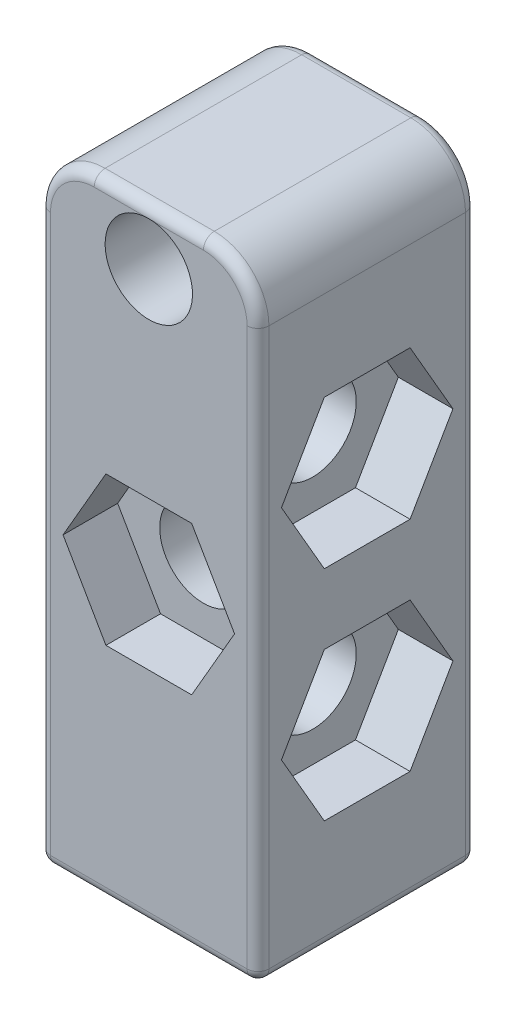
SolidWorks part; units mm, degrees
ref_plane "Alzado" through (0, 0, 0) normal (0, 0, 1) x (1, 0, 0)
ref_plane "Planta" through (0, 0, 0) normal (0, 1, 0) x (1, 0, 0)
ref_plane "Vista lateral" through (0, 0, 0) normal (1, 0, 0) x (0, 0, -1)
sketch "Croquis1" plane through (0, 0, 0) normal (0, 1, 0) x (1, 0, 0)
  line L1 (0, 0) -> (20, 0)
  line L2 (0, 0) -> (0, 20)
  line L3 (0, 20) -> (20, 20)
  line L4 (20, 0) -> (20, 20)
  dimension "D1" = 20
  dimension "D2" = 20
extrude "Saliente-Extruir1" add sketch "Croquis1" along normal blind 50 and the other way blind 7
sketch "Croquis2" plane through (0, 0, 0) normal (0, 0, 1) x (1, 0, 0)
  line L0 (0, 50) -> (0, -7) construction
  line L1 (0, 50) -> (20, 50) construction
  circle A0 centre (10, 45) radius 4
  circle A1 centre (10, 20) radius 4
  dimension "D1" = 8
  dimension "D2" = 8
  dimension "D3" = 10
  dimension "D4" = 5
  dimension "D5" = 25
extrude "Cortar-Extruir1" cut sketch "Croquis2" against normal through all
sketch "Croquis3" plane through (0, 0, 0) normal (0, 0, 1) x (1, 0, 0)
  line L1 (13.926, 26.8) -> (6.074, 26.8)
  line L2 (6.074, 26.8) -> (2.148, 20)
  line L3 (2.148, 20) -> (6.074, 13.2)
  line L4 (6.074, 13.2) -> (13.926, 13.2)
  line L5 (13.926, 13.2) -> (17.852, 20)
  line L6 (17.852, 20) -> (13.926, 26.8)
  circle A0 centre (10, 20) radius 7.852 construction
  dimension "D1" = 13.6
extrude "Cortar-Extruir2" cut sketch "Croquis3" against normal blind 5
sketch "Croquis4" plane through (0, 0, 0) normal (-1, 0, 0) x (0, 0, 1)
  line L0 (-20, 45) -> (0, 45) construction
  line L1 (-20, 50) -> (-20, -7) construction
  circle A0 centre (-10, 30) radius 4
  circle A1 centre (-10, 10) radius 4
  dimension "D1" = 8
  dimension "D2" = 8
  dimension "D5" = 10
  dimension "D3" = 15
  dimension "D4" = 20
extrude "Cortar-Extruir3" cut sketch "Croquis4" against normal through all
sketch "Croquis5" plane through (20, 0, 0) normal (-1, 0, 0) x (0, 0, 1)
  line L1 (-6.074, 23.2) -> (-2.148, 30)
  line L2 (-2.148, 30) -> (-6.074, 36.8)
  line L3 (-6.074, 36.8) -> (-13.926, 36.8)
  line L4 (-13.926, 36.8) -> (-17.852, 30)
  line L5 (-17.852, 30) -> (-13.926, 23.2)
  line L6 (-13.926, 23.2) -> (-6.074, 23.2)
  line L7 (-6.074, 16.8) -> (-13.926, 16.8)
  line L8 (-13.926, 16.8) -> (-17.852, 10)
  line L9 (-17.852, 10) -> (-13.926, 3.2)
  line L10 (-13.926, 3.2) -> (-6.074, 3.2)
  line L11 (-6.074, 3.2) -> (-2.148, 10)
  line L12 (-2.148, 10) -> (-6.074, 16.8)
  circle A0 centre (-10, 30) radius 6.8 construction
  circle A1 centre (-10, 10) radius 6.8 construction
  dimension "D1" = 13.6
  dimension "D2" = 13.6
extrude "Cortar-Extruir4" cut sketch "Croquis5" along normal blind 5
fillet "Redondeo1" radius 5 2 edges at (0, 50, -10) (20, 50, -10)
fillet "Redondeo2" radius 1 4 edges at (0, -7, -10) (10, -7, -20) (20, -7, -10) (10, -7, 0)
fillet "Redondeo3" radius 1 14 edges at (0.2929, -6.7071, -0.2929) (0, 19.5, 0) (1.4645, 48.5355, 0) (10, 50, 0) (18.5355, 48.5355, 0) (19.7071, -6.7071, -0.2929) (20, 19.5, 0) (0.2929, -6.7071, -19.7071) (0, 19.5, -20) (1.4645, 48.5355, -20) (10, 50, -20) (18.5355, 48.5355, -20) (19.7071, -6.7071, -19.7071) (20, 19.5, -20)
